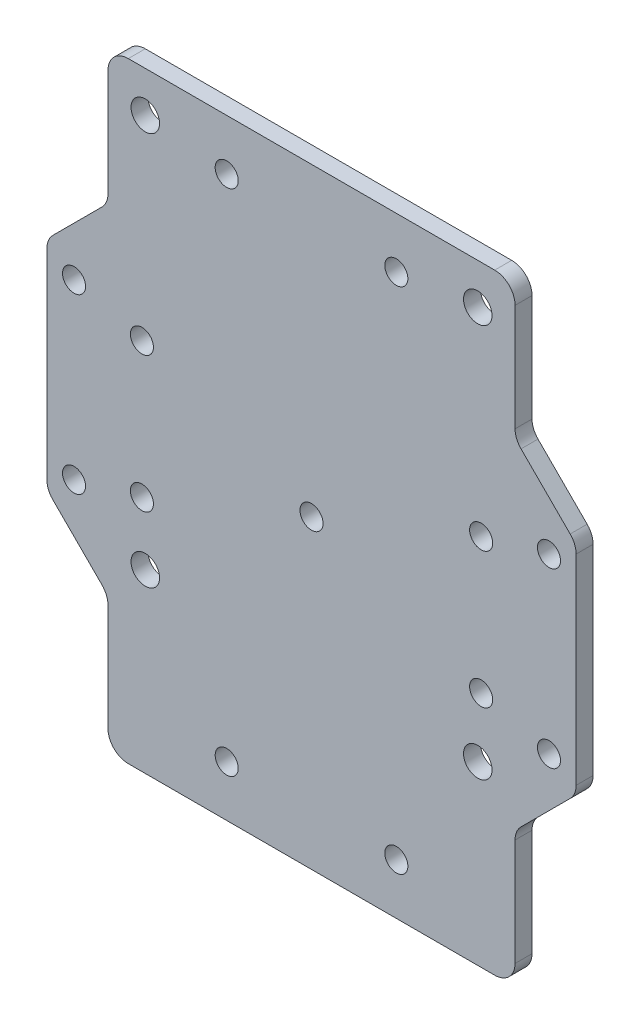
SolidWorks part; units mm, degrees
material "Thornel Mat VMA"
ref_plane "Front Plane" through (0, 0, 0) normal (0, 0, 1) x (1, 0, 0)
ref_plane "Top Plane" through (0, 0, 0) normal (0, 1, 0) x (1, 0, 0)
ref_plane "Right Plane" through (0, 0, 0) normal (1, 0, 0) x (0, 0, -1)
sketch "Sketch1" plane through (0, 0, 0) normal (0, 0, 1) x (1, 0, 0)
  line L0 (-39, -16) -> (-39, 16)
  line L5 (-30, 45) -> (30, 45)
  line L6 (-30, 45) -> (-30, -45)
  line L12 (-30, -45) -> (30, -45)
  line L17 (30, 45) -> (30, -45)
  line L19 (-30, 45) -> (30, -45) construction
  line L20 (-30, -45) -> (30, 45) construction
  line L21 (-39, 0) -> (39, 0) construction
  line L22 (-39, 16) -> (-30, 25)
  line L23 (-39, -16) -> (-30, -25)
  line L24 (0, 0) -> (0, 25) construction
  line L25 (39, -16) -> (30, -25)
  line L26 (39, 16) -> (30, 25)
  line L27 (39, -16) -> (39, 16)
  point P0 (0, 0)
  dimension "D1" = 60
  dimension "D2" = 90
  dimension "D3" = 9
  dimension "D4" = 16
  dimension "D5" = 135
extrude "Boss-Extrude1" add sketch "Sketch1" along normal mid plane 2.5 contours L5 | L17 L5 L6 L12 | L0 L23 L6 L22 | L25 L27 L26 L17 region at (-34.1707, 0, 0) region at (0, 0, 0) region at (34.1707, 0, 0)
fillet "Fillet1" radius 3 12 edges at (30, 45, 0) (30, -45, 0) (-30, -45, 0) (-30, 45, 0) (30, 25, 0) (39, 16, 0) (39, -16, 0) (30, -25, 0) (-30, -25, 0) (-39, -16, 0) (-39, 16, 0) (-30, 25, 0)
hole_wizard "Ø4.2 (4.2) Diameter Hole1" positions "Sketch2" profile "Sketch3" hole size "Ø4.2" standard "ANSI Metric" end condition through all
sketch "Sketch2" plane through (0, 0, -1.25) normal (0, 0, -1) x (-1, 0, 0)
  point P0 (-24.5, -19)
  point P3 (24.5, -19)
  point P6 (24.5, 39)
  point P9 (-24.5, 39)
sketch "Sketch3" plane through (24.5, -19, -1.25) normal (1, 0, 0) x (0, 1, 0)
  line L0 (0, 0) -> (0, 2.5)
  line L1 (0, 2.5) -> (2.1, 2.5)
  line L2 (2.1, 2.5) -> (2.1, 0)
  line L5 (2.1, 0) -> (0, 0)
  line L11 (0, -6.35) -> (0, 107.95) construction
  dimension "Thru Hole Dia." = 4.2
  dimension "Thru Hole Depth" = 2.5
hole_wizard "M3 Clearance Hole1" positions "Sketch4" profile "Sketch5" hole size "M3" standard "ANSI Metric" end condition through all
sketch "Sketch4" plane through (0, 0, -1.25) normal (0, 0, -1) x (-1, 0, 0)
  point P0 (-35, 12.75)
  point P3 (-35, -12.75)
  point P6 (35, -12.75)
  point P9 (35, 12.75)
sketch "Sketch5" plane through (35, 12.75, -1.25) normal (1, 0, 0) x (0, 1, 0)
  line L0 (0, 0) -> (0, 2.5)
  line L1 (0, 2.5) -> (1.7, 2.5)
  line L2 (1.7, 2.5) -> (1.7, 0)
  line L5 (1.7, 0) -> (0, 0)
  line L11 (0, -6.35) -> (0, 107.95) construction
  dimension "Thru Hole Dia." = 3.4
  dimension "Thru Hole Depth" = 2.5
hole_wizard "M3 Clearance Hole2" positions "Sketch6" profile "Sketch7" hole size "M3" standard "ANSI Metric" end condition through all
sketch "Sketch6" plane through (0, 0, 1.25) normal (0, 0, 1) x (1, 0, 0)
  point P0 (-12.5, -37.5)
  point P3 (12.5, -37.5)
  point P6 (-12.5, 37.5)
  point P9 (12.5, 37.5)
  point P12 (-25, 10)
  point P15 (-25, -10)
  point P18 (25, -10)
  point P21 (25, 10)
sketch "Sketch7" plane through (-12.5, -37.5, 1.25) normal (1, 0, 0) x (0, -1, 0)
  line L0 (0, 0) -> (0, 2.5)
  line L1 (0, 2.5) -> (1.7, 2.5)
  line L2 (1.7, 2.5) -> (1.7, 0)
  line L5 (1.7, 0) -> (0, 0)
  line L11 (0, -6.35) -> (0, 107.95) construction
  dimension "Thru Hole Dia." = 3.4
  dimension "Thru Hole Depth" = 2.5
hole_wizard "M3 Clearance Hole3" positions "Sketch8" profile "Sketch9" hole size "M3" standard "ANSI Metric" end condition through all
sketch "Sketch8" plane through (0, 0, 1.25) normal (0, 0, 1) x (1, 0, 0)
  point P0 (0, 0)
sketch "Sketch9" plane through (0, 0, 1.25) normal (1, 0, 0) x (0, -1, 0)
  line L0 (0, 0) -> (0, 2.5)
  line L1 (0, 2.5) -> (1.7, 2.5)
  line L2 (1.7, 2.5) -> (1.7, 0)
  line L5 (1.7, 0) -> (0, 0)
  line L11 (0, -6.35) -> (0, 107.95) construction
  dimension "Thru Hole Dia." = 3.4
  dimension "Thru Hole Depth" = 2.5
